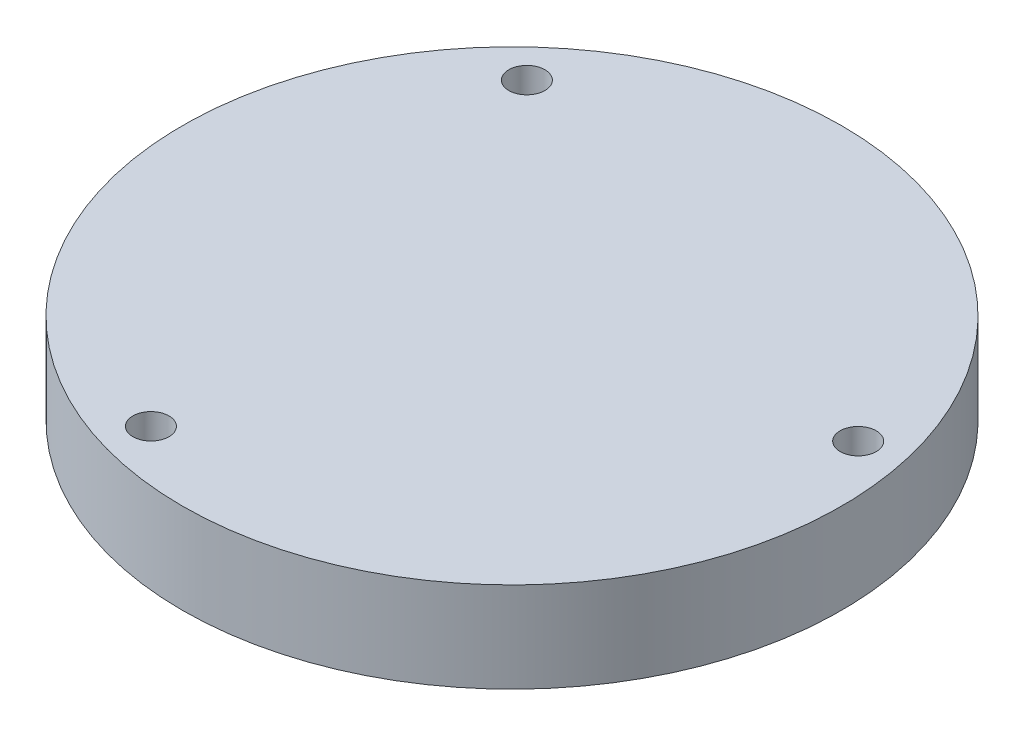
SolidWorks part; units mm, degrees
material "Acrylic (Medium-high impact)"
ref_plane "Front Plane" through (0, 0, 0) normal (0, 0, 1) x (1, 0, 0)
ref_plane "Top Plane" through (0, 0, 0) normal (0, 1, 0) x (1, 0, 0)
ref_plane "Right Plane" through (0, 0, 0) normal (1, 0, 0) x (0, 0, -1)
sketch "Sketch1" plane through (0, 0, 0) normal (0, 1, 0) x (1, 0, 0)
  circle A0 centre (0, 0) radius 36.5
  dimension "D1" = 73
extrude "Boss-Extrude1" add sketch "Sketch1" along normal blind 10
sketch "Sketch3" plane through (0, 10, 0) normal (0, 1, 0) x (1, 0, 0)
  circle A0 centre (-21.789, 23.4359) radius 2
  dimension "D1" = 4
  dimension "D2" = 32
extrude "Cut-Extrude1" cut sketch "Sketch3" against normal through all
pattern_circular "CirPattern1" count 3 every 120 about axis through (0, 10, 0) along (0, 1, 0) of "Cut-Extrude1"
